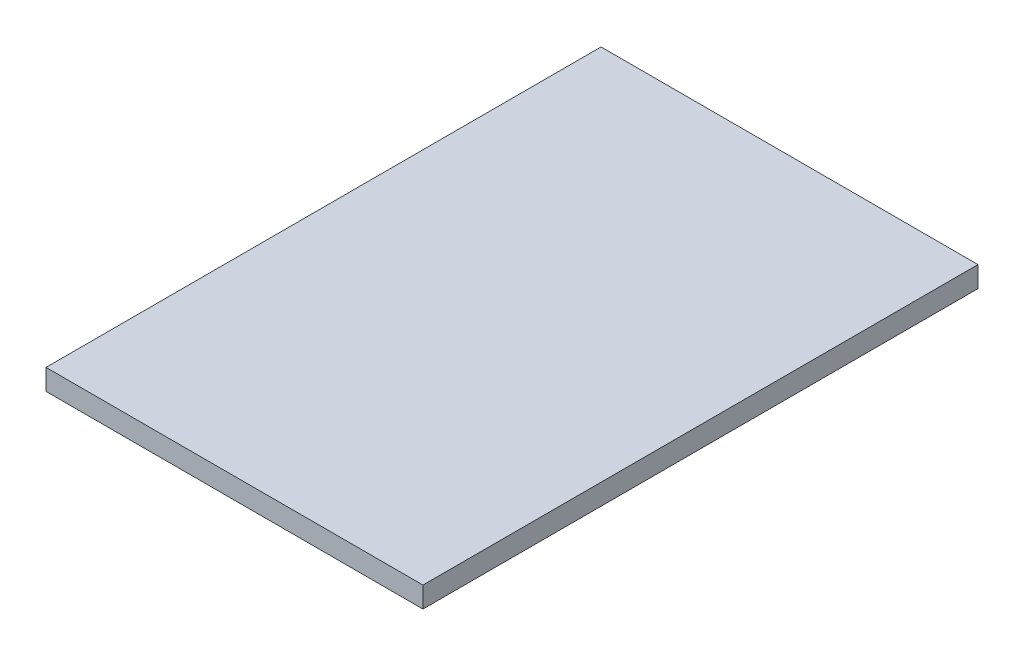
SolidWorks part; units mm, degrees
material "Perspex (TM) GS Acrylic Cast Sheet"
ref_plane "Front Plane" through (0, 0, 0) normal (0, 0, 1) x (1, 0, 0)
ref_plane "Top Plane" through (0, 0, 0) normal (0, 1, 0) x (1, 0, 0)
ref_plane "Right Plane" through (0, 0, 0) normal (1, 0, 0) x (0, 0, -1)
sketch "Sketch1" plane through (0, 0, 0) normal (0, 1, 0) x (1, 0, 0)
  line L1 (-81.5, -120) -> (81.5, -120)
  line L2 (-81.5, -120) -> (-81.5, 120)
  line L3 (-81.5, 120) -> (81.5, 120)
  line L4 (81.5, -120) -> (81.5, 120)
  line L5 (-81.5, -120) -> (81.5, 120) construction
  line L6 (-81.5, 120) -> (81.5, -120) construction
  point P0 (0, 0)
  dimension "D1" = 163
  dimension "D2" = 240
extrude "Boss-Extrude1" add sketch "Sketch1" along normal blind 9
sketch "Sketch2" plane through (0, 9, 0) normal (0, 1, 0) x (1, 0, 0)
  line L14 (-72.5, -111) -> (72.5, -111)
  line L15 (72.5, -111) -> (72.5, 111)
  line L16 (72.5, 111) -> (-72.5, 111)
  line L17 (-72.5, 111) -> (-72.5, -111)
  line L18 (-72.5, -111) -> (72.5, -111)
  line L19 (72.5, -111) -> (72.5, 111)
  line L20 (72.5, 111) -> (-72.5, 111)
  line L21 (-72.5, 111) -> (-72.5, -111)
  dimension "D1" = 9
equation "\"PCLength\"= 145mm'Length across I/O from PS to GPU"
equation "\"PCWidth\"= 340mm'Distance of longest part parallel to GPU(ussually GPU)"
equation "\"PCHeight\"= 180mm'Tallest point with mobo laying flat"
equation "\"WallThickness\"= 9mm'Thickness of each outer tank wall"
equation "\"ThermoBarrierThickness\"= 6mm'Thickness of barrier between hot side and cold side"
equation "\"HotSideGap\"= 36mm'Space in the hot side for a pump"
equation "\"PCClearance\"= 40mm'Clearance from top of tank to top of PC"
equation "\"RadiatorHeight\"= 275mm'Final Height from ground of radiators"
equation "\"AirflowGap\"= 25mm'Distance between radiators and tank for airflow"
equation "\"VolumeSubtraction\"= 230mm"
equation "\"D1@Sketch1\"=\"PCLength\" + (2 * \"WallThickness\")"
equation "\"D1@Boss-Extrude1\"=\"WallThickness\""
equation "\"D2@Sketch1\"=\"PCHeight\" + \"ThermoBarrierThickness\" + \"HotSideGap\" + (2 * \"WallThickness\")"
